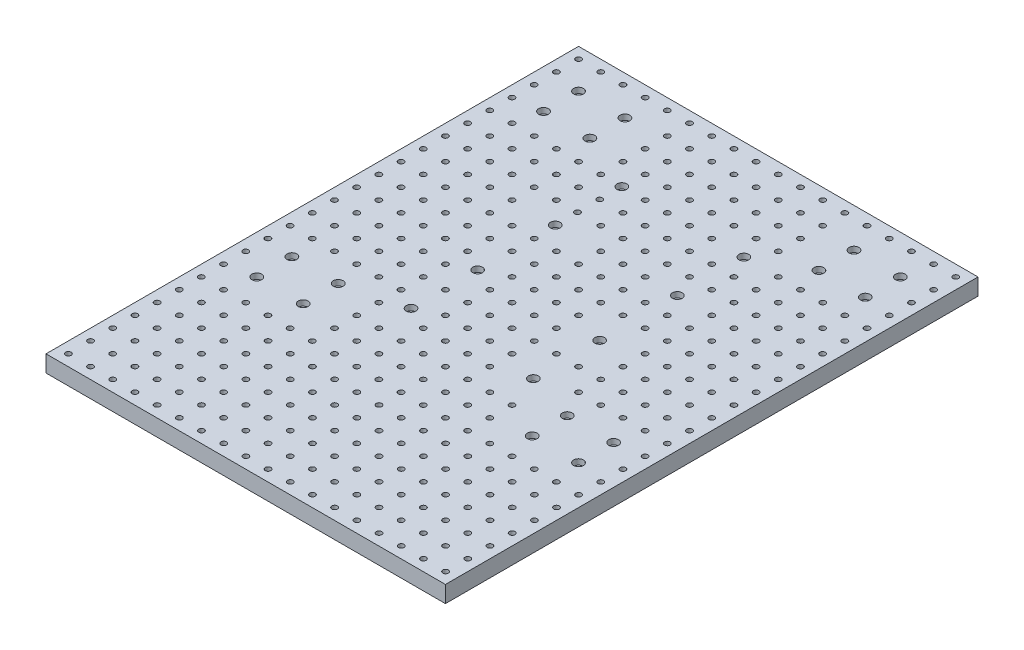
SolidWorks part; units mm, degrees
ref_plane "Front Plane" through (0, 0, 0) normal (0, 0, 1) x (1, 0, 0)
ref_plane "Top Plane" through (0, 0, 0) normal (0, 1, 0) x (1, 0, 0)
ref_plane "Right Plane" through (0, 0, 0) normal (1, 0, 0) x (0, 0, -1)
sketch "Sketch1" plane through (0, 0, 0) normal (0, 1, 0) x (1, 0, 0)
  line L0 (-187.6937, 187.6937) -> (228.6, -228.6) construction
  line L2 (-228.6, -228.6) -> (-228.6, 228.6)
  line L3 (-228.6, 228.6) -> (228.6, 228.6)
  line L4 (228.6, -228.6) -> (228.6, 228.6)
  line L5 (-228.6, -228.6) -> (186.3053, 186.3053) construction
  line L6 (-228.6, 228.6) -> (-193.3063, 193.3063) construction
  line L7 (213.6549, 213.6549) -> (228.6, 228.6) construction
  line L10 (-228.6, -228.6) -> (-228.6, -381)
  line L11 (-228.6, -381) -> (228.6, -381)
  line L12 (228.6, -228.6) -> (228.6, -381)
  circle A0 centre (-64.77, 114.3) radius 3.175
  circle A1 centre (74.93, 114.3) radius 3.175
  circle A2 centre (-64.77, 38.1) radius 3.175
  circle A3 centre (74.93, 38.1) radius 3.175
  circle A4 centre (131.064, 184.15) radius 3.048
  circle A5 centre (184.15, 184.15) radius 3.048
  circle A6 centre (184.15, 144.018) radius 3.048
  circle A7 centre (131.064, 144.018) radius 3.048
  circle A8 centre (131.064, -144.018) radius 3.048
  circle A9 centre (184.15, -144.018) radius 3.048
  circle A10 centre (131.064, -184.15) radius 3.048
  circle A11 centre (184.15, -184.15) radius 3.048
  circle A12 centre (-184.15, -144.018) radius 3.048
  circle A13 centre (-131.064, -144.018) radius 3.048
  circle A14 centre (-184.15, -184.15) radius 3.048
  circle A15 centre (-131.064, -184.15) radius 3.048
  circle A16 centre (-184.15, 144.018) radius 3.048
  circle A17 centre (-131.064, 144.018) radius 3.048
  circle A18 centre (-131.064, 184.15) radius 3.048
  circle A20 centre (-184.15, 184.15) radius 3.048
  circle A21 centre (-215.9, -215.9) radius 3.175
  circle A22 centre (-190.5, -215.9) radius 3.175
  circle A23 centre (-165.1, -215.9) radius 3.175
  circle A24 centre (-139.7, -215.9) radius 3.175
  circle A25 centre (-114.3, -215.9) radius 3.175
  circle A26 centre (-88.9, -215.9) radius 3.175
  circle A27 centre (-63.5, -215.9) radius 3.175
  circle A28 centre (-38.1, -215.9) radius 3.175
  circle A29 centre (-12.7, -215.9) radius 3.175
  circle A30 centre (12.7, -215.9) radius 3.175
  circle A31 centre (38.1, -215.9) radius 3.175
  circle A32 centre (63.5, -215.9) radius 3.175
  circle A33 centre (88.9, -215.9) radius 3.175
  circle A34 centre (114.3, -215.9) radius 3.175
  circle A35 centre (139.7, -215.9) radius 3.175
  circle A36 centre (165.1, -215.9) radius 3.175
  circle A37 centre (190.5, -215.9) radius 3.175
  circle A38 centre (215.9, -215.9) radius 3.175
  circle A43 centre (-88.9, -190.5) radius 3.175
  circle A44 centre (-63.5, -190.5) radius 3.175
  circle A45 centre (-38.1, -190.5) radius 3.175
  circle A46 centre (-12.7, -190.5) radius 3.175
  circle A47 centre (12.7, -190.5) radius 3.175
  circle A48 centre (38.1, -190.5) radius 3.175
  circle A49 centre (63.5, -190.5) radius 3.175
  circle A50 centre (88.9, -190.5) radius 3.175
  circle A55 centre (215.9, -190.5) radius 3.175
  circle A60 centre (-88.9, -165.1) radius 3.175
  circle A61 centre (-63.5, -165.1) radius 3.175
  circle A62 centre (-38.1, -165.1) radius 3.175
  circle A63 centre (-12.7, -165.1) radius 3.175
  circle A64 centre (12.7, -165.1) radius 3.175
  circle A65 centre (38.1, -165.1) radius 3.175
  circle A66 centre (63.5, -165.1) radius 3.175
  circle A67 centre (88.9, -165.1) radius 3.175
  circle A72 centre (215.9, -165.1) radius 3.175
  circle A77 centre (-88.9, -139.7) radius 3.175
  circle A79 centre (-38.1, -139.7) radius 3.175
  circle A80 centre (-12.7, -139.7) radius 3.175
  circle A81 centre (12.7, -139.7) radius 3.175
  circle A82 centre (38.1, -139.7) radius 3.175
  circle A89 centre (215.9, -139.7) radius 3.175
  circle A90 centre (-190.5, -114.3) radius 3.175
  circle A91 centre (-165.1, -114.3) radius 3.175
  circle A92 centre (-139.7, -114.3) radius 3.175
  circle A93 centre (-114.3, -114.3) radius 3.175
  circle A94 centre (-88.9, -114.3) radius 3.175
  circle A96 centre (-38.1, -114.3) radius 3.175
  circle A97 centre (-12.7, -114.3) radius 3.175
  circle A98 centre (12.7, -114.3) radius 3.175
  circle A99 centre (38.1, -114.3) radius 3.175
  circle A102 centre (114.3, -114.3) radius 3.175
  circle A103 centre (139.7, -114.3) radius 3.175
  circle A104 centre (165.1, -114.3) radius 3.175
  circle A105 centre (190.5, -114.3) radius 3.175
  circle A106 centre (215.9, -114.3) radius 3.175
  circle A107 centre (-190.5, -88.9) radius 3.175
  circle A108 centre (-165.1, -88.9) radius 3.175
  circle A109 centre (-139.7, -88.9) radius 3.175
  circle A110 centre (-114.3, -88.9) radius 3.175
  circle A111 centre (-88.9, -88.9) radius 3.175
  circle A112 centre (-63.5, -88.9) radius 3.175
  circle A113 centre (-38.1, -88.9) radius 3.175
  circle A114 centre (-12.7, -88.9) radius 3.175
  circle A115 centre (12.7, -88.9) radius 3.175
  circle A116 centre (38.1, -88.9) radius 3.175
  circle A117 centre (63.5, -88.9) radius 3.175
  circle A118 centre (88.9, -88.9) radius 3.175
  circle A119 centre (114.3, -88.9) radius 3.175
  circle A120 centre (139.7, -88.9) radius 3.175
  circle A121 centre (165.1, -88.9) radius 3.175
  circle A122 centre (190.5, -88.9) radius 3.175
  circle A123 centre (215.9, -88.9) radius 3.175
  circle A124 centre (-190.5, -63.5) radius 3.175
  circle A125 centre (-165.1, -63.5) radius 3.175
  circle A126 centre (-139.7, -63.5) radius 3.175
  circle A127 centre (-114.3, -63.5) radius 3.175
  circle A128 centre (-88.9, -63.5) radius 3.175
  circle A130 centre (-38.1, -63.5) radius 3.175
  circle A131 centre (-12.7, -63.5) radius 3.175
  circle A132 centre (12.7, -63.5) radius 3.175
  circle A133 centre (38.1, -63.5) radius 3.175
  circle A136 centre (114.3, -63.5) radius 3.175
  circle A137 centre (139.7, -63.5) radius 3.175
  circle A138 centre (165.1, -63.5) radius 3.175
  circle A139 centre (190.5, -63.5) radius 3.175
  circle A140 centre (215.9, -63.5) radius 3.175
  circle A141 centre (-190.5, -38.1) radius 3.175
  circle A142 centre (-165.1, -38.1) radius 3.175
  circle A143 centre (-139.7, -38.1) radius 3.175
  circle A144 centre (-114.3, -38.1) radius 3.175
  circle A145 centre (-88.9, -38.1) radius 3.175
  circle A147 centre (-38.1, -38.1) radius 3.175
  circle A148 centre (-12.7, -38.1) radius 3.175
  circle A149 centre (12.7, -38.1) radius 3.175
  circle A150 centre (38.1, -38.1) radius 3.175
  circle A153 centre (114.3, -38.1) radius 3.175
  circle A154 centre (139.7, -38.1) radius 3.175
  circle A155 centre (165.1, -38.1) radius 3.175
  circle A156 centre (190.5, -38.1) radius 3.175
  circle A157 centre (215.9, -38.1) radius 3.175
  circle A158 centre (-190.5, -12.7) radius 3.175
  circle A159 centre (-165.1, -12.7) radius 3.175
  circle A160 centre (-139.7, -12.7) radius 3.175
  circle A161 centre (-114.3, -12.7) radius 3.175
  circle A162 centre (-88.9, -12.7) radius 3.175
  circle A163 centre (-63.5, -12.7) radius 3.175
  circle A164 centre (-38.1, -12.7) radius 3.175
  circle A165 centre (-12.7, -12.7) radius 3.175
  circle A166 centre (12.7, -12.7) radius 3.175
  circle A167 centre (38.1, -12.7) radius 3.175
  circle A168 centre (63.5, -12.7) radius 3.175
  circle A169 centre (88.9, -12.7) radius 3.175
  circle A170 centre (114.3, -12.7) radius 3.175
  circle A171 centre (139.7, -12.7) radius 3.175
  circle A172 centre (165.1, -12.7) radius 3.175
  circle A173 centre (190.5, -12.7) radius 3.175
  circle A174 centre (215.9, -12.7) radius 3.175
  circle A175 centre (-190.5, 12.7) radius 3.175
  circle A176 centre (-165.1, 12.7) radius 3.175
  circle A177 centre (-139.7, 12.7) radius 3.175
  circle A178 centre (-114.3, 12.7) radius 3.175
  circle A182 centre (-12.7, 12.7) radius 3.175
  circle A183 centre (12.7, 12.7) radius 3.175
  circle A188 centre (139.7, 12.7) radius 3.175
  circle A189 centre (165.1, 12.7) radius 3.175
  circle A190 centre (190.5, 12.7) radius 3.175
  circle A191 centre (215.9, 12.7) radius 3.175
  circle A192 centre (-190.5, 38.1) radius 3.175
  circle A193 centre (-165.1, 38.1) radius 3.175
  circle A194 centre (-139.7, 38.1) radius 3.175
  circle A195 centre (-114.3, 38.1) radius 3.175
  circle A199 centre (-12.7, 38.1) radius 3.175
  circle A200 centre (12.7, 38.1) radius 3.175
  circle A205 centre (139.7, 38.1) radius 3.175
  circle A206 centre (165.1, 38.1) radius 3.175
  circle A207 centre (190.5, 38.1) radius 3.175
  circle A208 centre (215.9, 38.1) radius 3.175
  circle A209 centre (-190.5, 63.5) radius 3.175
  circle A210 centre (-165.1, 63.5) radius 3.175
  circle A211 centre (-139.7, 63.5) radius 3.175
  circle A212 centre (-114.3, 63.5) radius 3.175
  circle A216 centre (-12.7, 63.5) radius 3.175
  circle A217 centre (12.7, 63.5) radius 3.175
  circle A222 centre (139.7, 63.5) radius 3.175
  circle A223 centre (165.1, 63.5) radius 3.175
  circle A224 centre (190.5, 63.5) radius 3.175
  circle A225 centre (215.9, 63.5) radius 3.175
  circle A226 centre (-190.5, 88.9) radius 3.175
  circle A227 centre (-165.1, 88.9) radius 3.175
  circle A228 centre (-139.7, 88.9) radius 3.175
  circle A229 centre (-114.3, 88.9) radius 3.175
  circle A233 centre (-12.7, 88.9) radius 3.175
  circle A234 centre (12.7, 88.9) radius 3.175
  circle A239 centre (139.7, 88.9) radius 3.175
  circle A240 centre (165.1, 88.9) radius 3.175
  circle A241 centre (190.5, 88.9) radius 3.175
  circle A242 centre (215.9, 88.9) radius 3.175
  circle A243 centre (-190.5, 114.3) radius 3.175
  circle A244 centre (-165.1, 114.3) radius 3.175
  circle A245 centre (-139.7, 114.3) radius 3.175
  circle A246 centre (-114.3, 114.3) radius 3.175
  circle A250 centre (-12.7, 114.3) radius 3.175
  circle A251 centre (12.7, 114.3) radius 3.175
  circle A256 centre (139.7, 114.3) radius 3.175
  circle A257 centre (165.1, 114.3) radius 3.175
  circle A258 centre (190.5, 114.3) radius 3.175
  circle A259 centre (215.9, 114.3) radius 3.175
  circle A267 centre (-12.7, 139.7) radius 3.175
  circle A268 centre (12.7, 139.7) radius 3.175
  circle A276 centre (215.9, 139.7) radius 3.175
  circle A281 centre (-88.9, 165.1) radius 3.175
  circle A282 centre (-63.5, 165.1) radius 3.175
  circle A283 centre (-38.1, 165.1) radius 3.175
  circle A284 centre (-12.7, 165.1) radius 3.175
  circle A285 centre (12.7, 165.1) radius 3.175
  circle A286 centre (38.1, 165.1) radius 3.175
  circle A287 centre (63.5, 165.1) radius 3.175
  circle A288 centre (88.9, 165.1) radius 3.175
  circle A293 centre (215.9, 165.1) radius 3.175
  circle A298 centre (-88.9, 190.5) radius 3.175
  circle A299 centre (-63.5, 190.5) radius 3.175
  circle A300 centre (-38.1, 190.5) radius 3.175
  circle A301 centre (-12.7, 190.5) radius 3.175
  circle A302 centre (12.7, 190.5) radius 3.175
  circle A303 centre (38.1, 190.5) radius 3.175
  circle A304 centre (63.5, 190.5) radius 3.175
  circle A305 centre (88.9, 190.5) radius 3.175
  circle A310 centre (215.9, 190.5) radius 3.175
  circle A311 centre (-190.5, 215.9) radius 3.175
  circle A312 centre (-165.1, 215.9) radius 3.175
  circle A313 centre (-139.7, 215.9) radius 3.175
  circle A314 centre (-114.3, 215.9) radius 3.175
  circle A315 centre (-88.9, 215.9) radius 3.175
  circle A316 centre (-63.5, 215.9) radius 3.175
  circle A317 centre (-38.1, 215.9) radius 3.175
  circle A318 centre (-12.7, 215.9) radius 3.175
  circle A319 centre (12.7, 215.9) radius 3.175
  circle A320 centre (38.1, 215.9) radius 3.175
  circle A321 centre (63.5, 215.9) radius 3.175
  circle A322 centre (88.9, 215.9) radius 3.175
  circle A323 centre (114.3, 215.9) radius 3.175
  circle A324 centre (139.7, 215.9) radius 3.175
  circle A325 centre (165.1, 215.9) radius 3.175
  circle A326 centre (190.5, 215.9) radius 3.175
  circle A327 centre (215.9, 215.9) radius 3.175
  circle A328 centre (-215.9, -190.5) radius 3.175
  circle A329 centre (-215.9, -165.1) radius 3.175
  circle A330 centre (-215.9, -139.7) radius 3.175
  circle A331 centre (-215.9, -114.3) radius 3.175
  circle A332 centre (-215.9, -88.9) radius 3.175
  circle A333 centre (-215.9, -63.5) radius 3.175
  circle A334 centre (-215.9, -38.1) radius 3.175
  circle A335 centre (-215.9, -12.7) radius 3.175
  circle A336 centre (-215.9, 12.7) radius 3.175
  circle A337 centre (-215.9, 38.1) radius 3.175
  circle A338 centre (-215.9, 63.5) radius 3.175
  circle A339 centre (-215.9, 88.9) radius 3.175
  circle A340 centre (-215.9, 114.3) radius 3.175
  circle A341 centre (-215.9, 139.7) radius 3.175
  circle A342 centre (-215.9, 165.1) radius 3.175
  circle A343 centre (-215.9, 190.5) radius 3.175
  circle A344 centre (-215.9, 215.9) radius 3.175
  circle A345 centre (38.1, 12.7) radius 3.175
  circle A346 centre (63.5, 12.7) radius 3.175
  circle A347 centre (88.9, 12.7) radius 3.175
  circle A348 centre (114.3, 12.7) radius 3.175
  circle A349 centre (38.1, 38.1) radius 3.175
  circle A350 centre (38.1, 63.5) radius 3.175
  circle A351 centre (38.1, 88.9) radius 3.175
  circle A352 centre (38.1, 139.7) radius 3.175
  circle A353 centre (38.1, 114.3) radius 3.175
  circle A354 centre (63.5, 139.7) radius 3.175
  circle A355 centre (88.9, 139.7) radius 3.175
  circle A356 centre (63.5, 88.9) radius 3.175
  circle A357 centre (88.9, 88.9) radius 3.175
  circle A358 centre (114.3, 88.9) radius 3.175
  circle A359 centre (63.5, 63.5) radius 3.175
  circle A360 centre (88.9, 63.5) radius 3.175
  circle A361 centre (114.3, 63.5) radius 3.175
  circle A362 centre (114.3, 38.1) radius 3.175
  circle A363 centre (-64.77, -127) radius 3.175
  circle A365 centre (-64.77, -127) radius 5.5562
  circle A366 centre (74.93, -126.6483) radius 3.175
  circle A368 centre (74.93, -126.6483) radius 5.5563
  circle A380 centre (131.064, 184.15) radius 5.588
  circle A381 centre (-184.15, 144.018) radius 5.588
  circle A382 centre (-131.064, 144.018) radius 5.588
  circle A383 centre (-131.064, 184.15) radius 5.588
  circle A384 centre (-184.15, 184.15) radius 5.588
  circle A385 centre (-184.15, -144.018) radius 5.588
  circle A386 centre (-184.15, -184.15) radius 5.588
  circle A387 centre (-131.064, -144.018) radius 5.588
  circle A388 centre (-131.064, -184.15) radius 5.588
  circle A389 centre (131.064, -144.018) radius 5.588
  circle A390 centre (131.064, -184.15) radius 5.588
  circle A391 centre (184.15, -144.018) radius 5.588
  circle A392 centre (184.15, -184.15) radius 5.588
  circle A393 centre (184.15, 184.15) radius 5.588
  circle A394 centre (131.064, 144.018) radius 5.588
  circle A395 centre (184.15, 144.018) radius 5.588
  circle A396 centre (-88.9, 114.3) radius 3.175
  circle A397 centre (-38.1, 114.3) radius 3.175
  circle A398 centre (114.3, 114.3) radius 3.175
  circle A399 centre (-215.9, -241.1325) radius 3.175
  circle A402 centre (-190.5, -241.1325) radius 3.175
  circle A403 centre (-165.1, -241.1325) radius 3.175
  circle A404 centre (-139.7, -241.1325) radius 3.175
  circle A405 centre (-114.3, -241.1325) radius 3.175
  circle A406 centre (-88.9, -241.1325) radius 3.175
  circle A407 centre (-63.5, -241.1325) radius 3.175
  circle A408 centre (-38.1, -241.1325) radius 3.175
  circle A409 centre (-12.7, -241.1325) radius 3.175
  circle A410 centre (12.7, -241.1325) radius 3.175
  circle A411 centre (38.1, -241.1325) radius 3.175
  circle A412 centre (63.5, -241.1325) radius 3.175
  circle A413 centre (88.9, -241.1325) radius 3.175
  circle A414 centre (114.3, -241.1325) radius 3.175
  circle A415 centre (139.7, -241.1325) radius 3.175
  circle A416 centre (165.1, -241.1325) radius 3.175
  circle A417 centre (190.5, -241.1325) radius 3.175
  circle A418 centre (215.9, -241.1325) radius 3.175
  circle A419 centre (-190.5, -266.5325) radius 3.175
  circle A420 centre (-165.1, -266.5325) radius 3.175
  circle A421 centre (-139.7, -266.5325) radius 3.175
  circle A422 centre (-114.3, -266.5325) radius 3.175
  circle A423 centre (-88.9, -266.5325) radius 3.175
  circle A424 centre (-63.5, -266.5325) radius 3.175
  circle A425 centre (-38.1, -266.5325) radius 3.175
  circle A426 centre (-12.7, -266.5325) radius 3.175
  circle A427 centre (12.7, -266.5325) radius 3.175
  circle A428 centre (38.1, -266.5325) radius 3.175
  circle A429 centre (63.5, -266.5325) radius 3.175
  circle A430 centre (88.9, -266.5325) radius 3.175
  circle A431 centre (114.3, -266.5325) radius 3.175
  circle A432 centre (139.7, -266.5325) radius 3.175
  circle A433 centre (165.1, -266.5325) radius 3.175
  circle A434 centre (-64.77, 114.3) radius 5.5562
  circle A435 centre (74.93, 114.3) radius 5.5563
  circle A436 centre (74.93, 38.1) radius 5.5563
  circle A437 centre (-64.77, 38.1) radius 5.5562
  circle A438 centre (190.5, -266.5325) radius 3.175
  circle A439 centre (-64.77, -50.8) radius 3.175
  circle A440 centre (-64.77, -50.8) radius 5.5562
  circle A441 centre (215.9, -266.5325) radius 3.175
  circle A442 centre (74.93, -50.8) radius 3.175
  circle A443 centre (74.93, -50.8) radius 5.5563
  circle A445 centre (-63.5, 12.7) radius 3.175
  circle A446 centre (-38.1, 12.7) radius 3.175
  circle A447 centre (-88.9, 12.7) radius 3.175
  circle A448 centre (-88.9, 63.5) radius 3.175
  circle A449 centre (-38.1, 63.5) radius 3.175
  circle A450 centre (-64.77, 63.5) radius 3.175
  circle A451 centre (-88.9, 88.9) radius 3.175
  circle A452 centre (-38.1, 88.9) radius 3.175
  circle A453 centre (-64.77, 88.9) radius 3.175
  circle A454 centre (-88.9, 139.7) radius 3.175
  circle A456 centre (-38.1, 139.7) radius 3.175
  circle A457 centre (-63.5, 139.7) radius 3.175
  circle A458 centre (-190.5, -291.9325) radius 3.175
  circle A459 centre (-165.1, -291.9325) radius 3.175
  circle A460 centre (-139.7, -291.9325) radius 3.175
  circle A461 centre (-114.3, -291.9325) radius 3.175
  circle A462 centre (-88.9, -291.9325) radius 3.175
  circle A463 centre (-63.5, -291.9325) radius 3.175
  circle A464 centre (-38.1, -291.9325) radius 3.175
  circle A465 centre (-12.7, -291.9325) radius 3.175
  circle A466 centre (12.7, -291.9325) radius 3.175
  circle A467 centre (38.1, -291.9325) radius 3.175
  circle A468 centre (63.5, -291.9325) radius 3.175
  circle A469 centre (88.9, -291.9325) radius 3.175
  circle A470 centre (114.3, -291.9325) radius 3.175
  circle A471 centre (139.7, -291.9325) radius 3.175
  circle A472 centre (165.1, -291.9325) radius 3.175
  circle A473 centre (190.5, -291.9325) radius 3.175
  circle A474 centre (215.9, -291.9325) radius 3.175
  circle A475 centre (-190.5, -317.3325) radius 3.175
  circle A476 centre (-165.1, -317.3325) radius 3.175
  circle A477 centre (-139.7, -317.3325) radius 3.175
  circle A478 centre (-114.3, -317.3325) radius 3.175
  circle A479 centre (-88.9, -317.3325) radius 3.175
  circle A480 centre (-63.5, -317.3325) radius 3.175
  circle A481 centre (-38.1, -317.3325) radius 3.175
  circle A482 centre (-12.7, -317.3325) radius 3.175
  circle A483 centre (12.7, -317.3325) radius 3.175
  circle A484 centre (38.1, -317.3325) radius 3.175
  circle A485 centre (63.5, -317.3325) radius 3.175
  circle A486 centre (88.9, -317.3325) radius 3.175
  circle A487 centre (114.3, -317.3325) radius 3.175
  circle A488 centre (139.7, -317.3325) radius 3.175
  circle A489 centre (165.1, -317.3325) radius 3.175
  circle A490 centre (190.5, -317.3325) radius 3.175
  circle A491 centre (215.9, -317.3325) radius 3.175
  circle A492 centre (-190.5, -342.7325) radius 3.175
  circle A493 centre (-165.1, -342.7325) radius 3.175
  circle A494 centre (-139.7, -342.7325) radius 3.175
  circle A495 centre (-114.3, -342.7325) radius 3.175
  circle A496 centre (-88.9, -342.7325) radius 3.175
  circle A497 centre (-63.5, -342.7325) radius 3.175
  circle A498 centre (-38.1, -342.7325) radius 3.175
  circle A499 centre (-12.7, -342.7325) radius 3.175
  circle A500 centre (12.7, -342.7325) radius 3.175
  circle A501 centre (38.1, -342.7325) radius 3.175
  circle A502 centre (63.5, -342.7325) radius 3.175
  circle A503 centre (88.9, -342.7325) radius 3.175
  circle A504 centre (114.3, -342.7325) radius 3.175
  circle A505 centre (139.7, -342.7325) radius 3.175
  circle A506 centre (165.1, -342.7325) radius 3.175
  circle A507 centre (190.5, -342.7325) radius 3.175
  circle A508 centre (215.9, -342.7325) radius 3.175
  circle A509 centre (-190.5, -368.1325) radius 3.175
  circle A510 centre (-165.1, -368.1325) radius 3.175
  circle A511 centre (-139.7, -368.1325) radius 3.175
  circle A512 centre (-114.3, -368.1325) radius 3.175
  circle A513 centre (-88.9, -368.1325) radius 3.175
  circle A514 centre (-63.5, -368.1325) radius 3.175
  circle A515 centre (-38.1, -368.1325) radius 3.175
  circle A516 centre (-12.7, -368.1325) radius 3.175
  circle A517 centre (12.7, -368.1325) radius 3.175
  circle A518 centre (38.1, -368.1325) radius 3.175
  circle A519 centre (63.5, -368.1325) radius 3.175
  circle A520 centre (88.9, -368.1325) radius 3.175
  circle A521 centre (114.3, -368.1325) radius 3.175
  circle A522 centre (139.7, -368.1325) radius 3.175
  circle A523 centre (165.1, -368.1325) radius 3.175
  circle A524 centre (190.5, -368.1325) radius 3.175
  circle A525 centre (215.9, -368.1325) radius 3.175
  circle A526 centre (-215.9, -266.5325) radius 3.175
  circle A527 centre (-215.9, -291.9325) radius 3.175
  circle A528 centre (-215.9, -317.3325) radius 3.175
  circle A529 centre (-215.9, -342.7325) radius 3.175
  circle A530 centre (-215.9, -368.1325) radius 3.175
  point P0 (0, 0)
  dimension "D21" = 6.096
  dimension "D22" = 11.176
  dimension "D23" = 11.176
  dimension "D24" = 11.176
  dimension "D25" = 6
  dimension "D26" = 6.096
  dimension "D27" = 457.2
  dimension "D28" = 6.096
  dimension "D36" = 6.096
  dimension "D37" = 6.35
  dimension "D63" = 11.1125
  dimension "D19" = 11.176
  dimension "D12" = 6.35
  dimension "D15" = 6.35
  dimension "D1" = 457.2
  dimension "D3" = 139.7
  dimension "D5" = 53.086
  dimension "D7" = 53.086
  dimension "D8" = 0
  dimension "D9" = 53.086
  dimension "D10" = 88.9
  dimension "D11" = 609.6
  dimension "D13" = 40.132
  dimension "D14" = 76.2
  dimension "D16" = 40.132
  dimension "D17" = 18
  dimension "D18" = 0
  dimension "D20" = 40.132
  dimension "D41" = 38.1
  dimension "D43" = 76.2
  dimension "D45" = 44.45
  dimension "D47" = 64.77
  dimension "D51" = 44.45
  dimension "D52" = 44.45
  dimension "D54" = 44.45
  dimension "D55" = 44.45
  dimension "D58" = 44.45
  dimension "D60" = 12.7
  dimension "D65" = 25.4
  dimension "D66" = 25.4
extrude "Boss-Extrude1" add sketch "Sketch1" along normal blind 19.05
extrude "Boss-Extrude2" add sketch "Sketch1<2>" along normal blind 12.7 contours A384 A20 | A383 A18 | A382 A17 | A381 | A434 | A435 | A437 | A436 | A440 | A443 | A365 | A385 | A386 | A388 | A387 | A368 | A389 | A390 | A392 | A391 | A380 | A393 | A395 | A394 region at (-136.4939, 0, -144.018) region at (-136.4939, 0, -184.15) region at (-189.5799, 0, -184.15)
sketch "Sketch1<2>" plane through (0, 0, 0) normal (0, 1, 0) x (1, 0, 0) same geometry as "Sketch1"
extrude "Cut-Extrude1" cut sketch "Sketch1<3>" against normal blind 50.8 from surface contours A20 | A18 | A17 | A16 | A0 | A1 | A2 | A3 | A439 | A442 | A363 | A366 | A8 | A10 | A11 | A9 | A12 | A14 | A13 | A15 | A4 | A5 | A7 | A6 starting at face at (0, 19.05, 76.2)
sketch "Sketch1<3>" plane through (0, 0, 0) normal (0, 1, 0) x (1, 0, 0) same geometry as "Sketch1"
